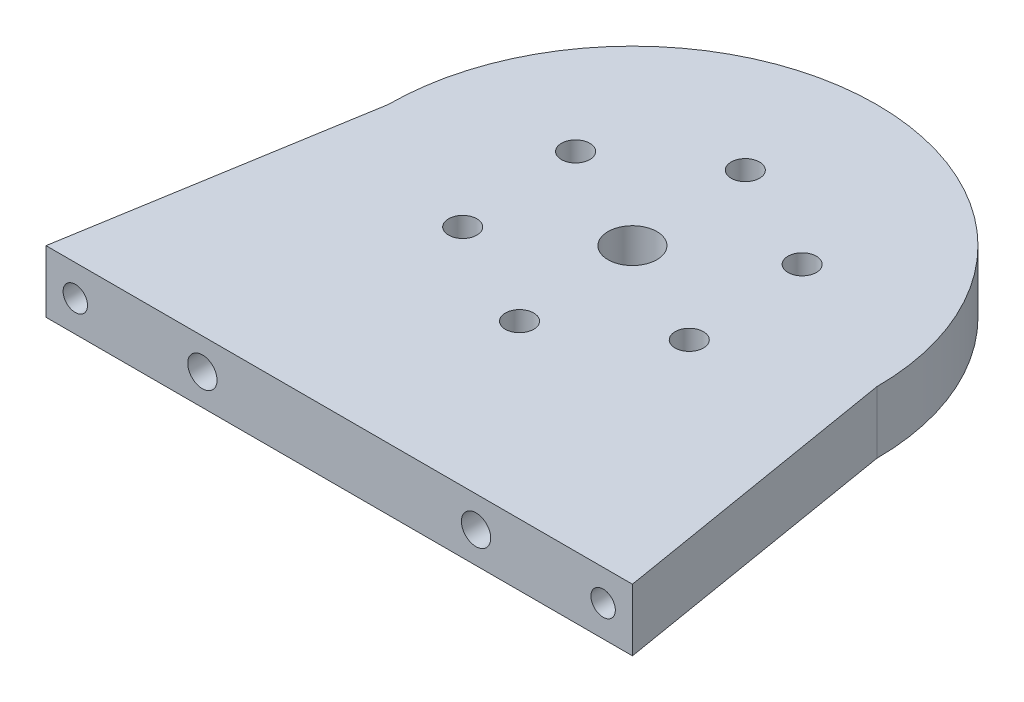
SolidWorks part; units mm, degrees
material "Aleación 6061"
ref_plane "Alzado" through (0, 0, 0) normal (0, 0, 1) x (1, 0, 0)
ref_plane "Planta" through (0, 0, 0) normal (0, 1, 0) x (1, 0, 0)
ref_plane "Vista lateral" through (0, 0, 0) normal (1, 0, 0) x (0, 0, -1)
ref_plane "Plano_xJ3" through (152.4, 0, 0) normal (1, 0, 0) x (0, 0, -1)
ref_plane "Plano_zJ5" through (0, 0, 336.55) normal (0, 0, 1) x (1, 0, 0)
ref_axis "Eje_J5" through (152.4, -30.8, 336.55) along (0, 1, 0)
ref_axis "Eje_J6" through (152.4, 0, 369.3) along (0, 0, -1)
sketch "Croquis8" plane through (0, 0, 0) normal (0, 1, 0) x (1, 0, 0)
  line L0 (127.4, -336.55) -> (177.4, -336.55)
  line L1 (177.4, -336.55) -> (182.4, -366.55)
  line L2 (182.4, -366.55) -> (122.4, -366.55)
  line L3 (122.4, -366.55) -> (127.4, -336.55)
  dimension "D1" = 127.4
  dimension "D2" = 336.55
  dimension "D3" = 177.4
  dimension "D4" = 336.55
  dimension "D5" = 182.4
  dimension "D6" = 366.55
  dimension "D7" = 122.4
  dimension "D8" = 366.55
extrude "Placa_J5" add sketch "Croquis8" along normal blind 6.35 from offset 3.175 offset against normal yes
sketch "Croquis9" plane through (0, 0, 0) normal (0, 1, 0) x (1, 0, 0)
  circle A0 centre (152.4, -336.55) radius 25
  dimension "D1" = 50
  dimension "D2" = 152.4
  dimension "D3" = 336.55
extrude "Placa_J5_redondeo" add sketch "Croquis9" along normal blind 6.35 from offset 3.175 offset against normal yes
sketch "Croquis10" plane through (0, 0, 0) normal (0, 1, 0) x (1, 0, 0)
  circle A0 centre (163.654, -341.9904) radius 1.45
  circle A1 centre (153.3155, -349.0164) radius 1.45
  circle A2 centre (142.0615, -343.576) radius 1.45
  circle A3 centre (141.146, -331.1096) radius 1.45
  circle A4 centre (151.4845, -324.0836) radius 1.45
  circle A5 centre (162.7385, -329.524) radius 1.45
  circle A6 centre (152.4, -336.55) radius 2.5
  dimension "D1" = 2.9
  dimension "D2" = 2.9
  dimension "D3" = 2.9
  dimension "D4" = 2.9
  dimension "D5" = 2.9
  dimension "D6" = 2.9
  dimension "D7" = 5
  dimension "D8" = 163.654
  dimension "D9" = 341.9904
  dimension "D10" = 153.3155
  dimension "D11" = 349.0164
  dimension "D12" = 142.0615
  dimension "D13" = 343.576
  dimension "D14" = 141.146
  dimension "D15" = 331.1096
  dimension "D16" = 151.4845
  dimension "D17" = 324.0836
  dimension "D18" = 162.7385
  dimension "D19" = 329.524
  dimension "D20" = 152.4
  dimension "D21" = 336.55
extrude "Barrenos_salida_M5" cut sketch "Croquis10" along normal blind 6.35 from offset 3.175 offset against normal yes
sketch "Croquis11" plane through (0, 0, 0) normal (0, 1, 0) x (1, 0, 0)
  circle A0 centre (163.654, -341.9904) radius 2.5
  circle A1 centre (153.3155, -349.0164) radius 2.5
  circle A2 centre (142.0615, -343.576) radius 2.5
  circle A3 centre (141.146, -331.1096) radius 2.5
  circle A4 centre (151.4845, -324.0836) radius 2.5
  circle A5 centre (162.7385, -329.524) radius 2.5
  dimension "D1" = 5
  dimension "D2" = 5
  dimension "D3" = 5
  dimension "D4" = 5
  dimension "D5" = 5
  dimension "D6" = 5
  dimension "D7" = 163.654
  dimension "D8" = 341.9904
  dimension "D9" = 153.3155
  dimension "D10" = 349.0164
  dimension "D11" = 142.0615
  dimension "D12" = 343.576
  dimension "D13" = 141.146
  dimension "D14" = 331.1096
  dimension "D15" = 151.4845
  dimension "D16" = 324.0836
  dimension "D17" = 162.7385
  dimension "D18" = 329.524
extrude "Refrentado_M2-5" cut sketch "Croquis11" along normal blind 2.6 from offset 3.175 offset against normal yes
sketch "Croquis12" plane through (0, 0, 0) normal (0, 0, 1) x (1, 0, 0)
  circle A0 centre (125.4, 0) radius 1.25
  circle A1 centre (179.4, 0) radius 1.25
  dimension "D1" = 2.5
  dimension "D2" = 2.5
  dimension "D3" = 125.4
  dimension "D4" = 179.4
extrude "Rosca_M3_canto" cut sketch "Croquis12" along normal blind 9 from offset 357.55
sketch "Croquis13" plane through (0, 0, 0) normal (0, 0, 1) x (1, 0, 0)
  circle A0 centre (138.4, 0) radius 1.5
  circle A1 centre (166.4, 0) radius 1.5
  dimension "D1" = 3
  dimension "D2" = 3
  dimension "D3" = 138.4
  dimension "D4" = 166.4
extrude "Pasadores_D3" cut sketch "Croquis13" along normal blind 7 from offset 359.55
